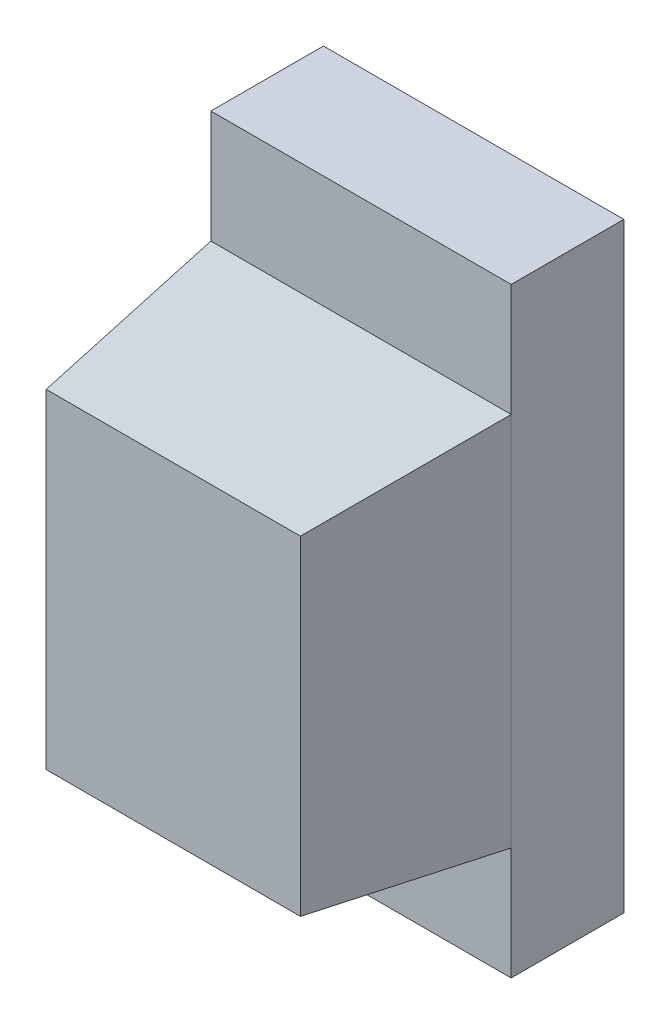
SolidWorks part; units mm, degrees
note: '?' marks a value the reader was unsure of.
ref_plane "Front Plane" through (0, 0, 0) normal (0, 0, 1) x (1, 0, 0)
ref_plane "Top Plane" through (0, 0, 0) normal (0, 1, 0) x (1, 0, 0)
ref_plane "Right Plane" through (0, 0, 0) normal (1, 0, 0) x (0, 0, -1)
sketch "Sketch1" plane through (0, 0, 0) normal (0, 0, 1) x (1, 0, 0)
  line L1 (-0.4, 0.8) -> (0.4, 0.8)
  line L2 (-0.4, 0.8) -> (-0.4, -0.8)
  line L3 (-0.4, -0.8) -> (0.4, -0.8)
  line L4 (0.4, 0.8) -> (0.4, -0.8)
  line L5 (-0.4, 0.8) -> (0.4, -0.8) construction
  line L6 (-0.4, -0.8) -> (0.4, 0.8) construction
  point P0 (0, 0)
  dimension "D1" = 0.8
  dimension "D2" = 1.6
extrude "Boss-Extrude1" add sketch "Sketch1" along normal blind 0.3
sketch "Sketch3" plane through (0, 0, 0.3) normal (0, 0, 1) x (1, 0, 0)
  line L0 (0.4, -0.8) -> (0.4, 0.8) construction
  line L1 (-0.4, -0.5) -> (0.4, -0.5)
  line L2 (-0.4, -0.5) -> (-0.4, 0.5)
  line L3 (-0.4, 0.5) -> (0.4, 0.5)
  line L4 (0.4, -0.5) -> (0.4, 0.5)
  line L5 (-0.4, -0.5) -> (0.4, 0.5) construction
  line L6 (-0.4, 0.5) -> (0.4, -0.5) construction
  line L7 (0.4, 0.8) -> (-0.4, 0.8) construction
  point P0 (0, 0)
  dimension "D1" = 0.3
extrude "Boss-Extrude3" add sketch "Sketch3" along normal offset from surface 0.8 draft 7
ref_axis "Axis1" through (0, 0, -0.04) along (0, 0, 1)?
